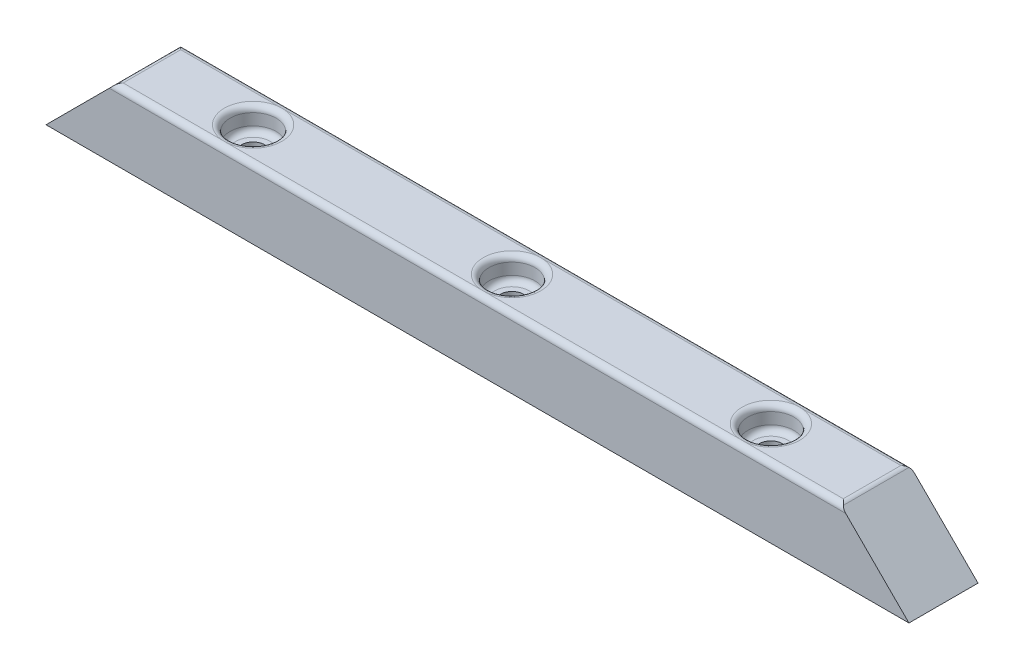
SolidWorks part; units mm, degrees
ref_plane "Front Plane" through (0, 0, 0) normal (0, 0, 1) x (1, 0, 0)
ref_plane "Top Plane" through (0, 0, 0) normal (0, 1, 0) x (1, 0, 0)
ref_plane "Right Plane" through (0, 0, 0) normal (1, 0, 0) x (0, 0, -1)
sketch "Sketch2" plane through (0, 0, 0) normal (0, 0, 1) x (1, 0, 0)
  line L0 (-75, -6) -> (-63, 6)
  line L1 (-75, -6) -> (75, -6)
  line L3 (-63, 6) -> (63, 6)
  line L5 (-75, -6) -> (63.8889, 5.1111) construction
  line L6 (-63.8889, 5.1111) -> (75, -6) construction
  line L7 (75, -6) -> (63, 6)
  point P0 (0, 0)
  dimension "D2" = 150
  dimension "D3" = 45
  dimension "D4" = 45
extrude "Boss-Extrude1" add sketch "Sketch2" along normal blind 12
sketch "Sketch3" plane through (0, 6, 0) normal (0, 1, 0) x (1, 0, 0)
  line L0 (63, -6) -> (-63, -6) construction
  line L1 (63, -12) -> (63, 0) construction
  line L2 (-63, -12) -> (-63, 0) construction
  circle A0 centre (0, -6) radius 2
  circle A1 centre (45, -6) radius 2
  circle A2 centre (-45, -6) radius 2
  point P12 (-50.0025, -6)
  point P13 (44.708, -6)
  dimension "D1" = 4
  dimension "D3" = 45
  dimension "D2" = 45
extrude "Cut-Extrude1" cut sketch "Sketch3" against normal blind 12
sketch "Sketch4" plane through (0, 6, 0) normal (0, 1, 0) x (1, 0, 0)
  circle A0 centre (-45, -6) radius 4
  circle A1 centre (0, -6) radius 4
  circle A2 centre (45, -6) radius 4
extrude "Cut-Extrude2" cut sketch "Sketch4" against normal blind 4
fillet "Fillet1" radius 1 3 edges at (-49, 6, 6) (41, 6, 6) (-4, 6, 6)
fillet "Fillet2" radius 1 3 edges at (-49, 2, 6) (-4, 2, 6) (41, 2, 6)
fillet "Fillet3" radius 1 4 edges at (-63, 6, 6) (63, 6, 6) (0, 6, 12) (0, 6, 0)
